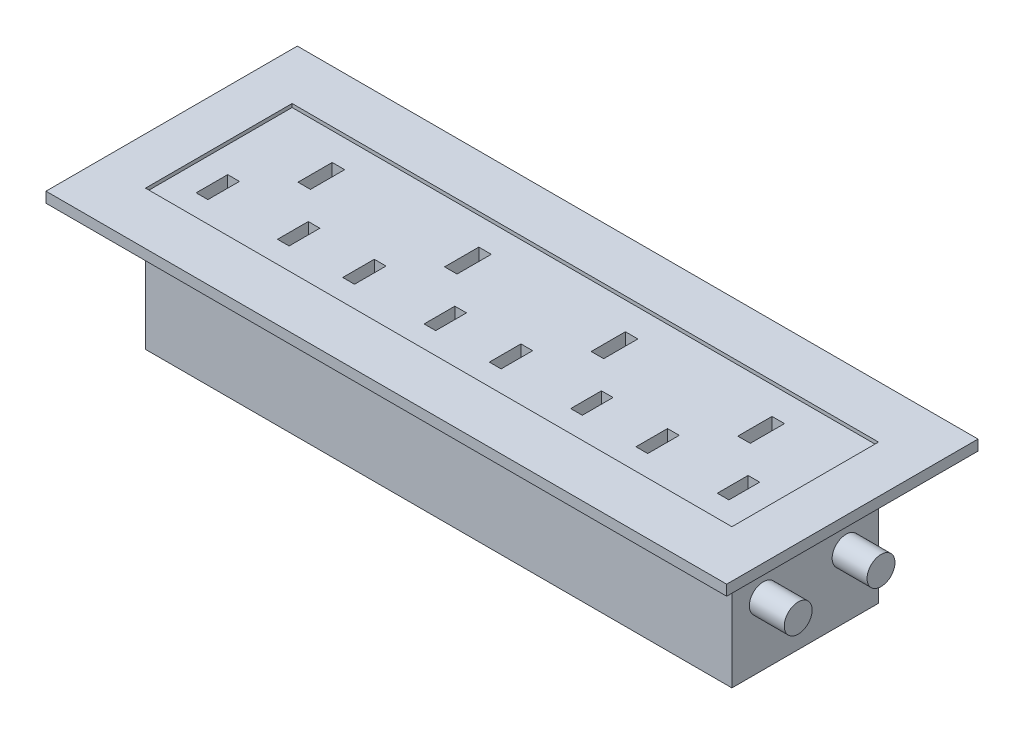
SolidWorks part; units mm, degrees
ref_plane "前视基准面" through (0, 0, 0) normal (0, 0, 1) x (1, 0, 0)
ref_plane "上视基准面" through (0, 0, 0) normal (0, 1, 0) x (1, 0, 0)
ref_plane "右视基准面" through (0, 0, 0) normal (1, 0, 0) x (0, 0, -1)
sketch "草图1" plane through (0, 0, 0) normal (0, 1, 0) x (1, 0, 0)
  line L1 (-97.5, 36) -> (97.5, 36)
  line L2 (-97.5, 36) -> (-97.5, -36)
  line L3 (-97.5, -36) -> (97.5, -36)
  line L4 (97.5, 36) -> (97.5, -36)
  line L5 (-97.5, 36) -> (97.5, -36) construction
  line L6 (-97.5, -36) -> (97.5, 36) construction
  point P0 (0, 0)
  dimension "D1" = 195
  dimension "D2" = 72
extrude "凸台-拉伸1" add sketch "草图1" along normal blind 3
sketch "草图2" plane through (0, 3, 0) normal (0, 1, 0) x (1, 0, 0)
  line L1 (-84, 21) -> (84, 21)
  line L2 (-84, 21) -> (-84, -21)
  line L3 (-84, -21) -> (84, -21)
  line L4 (84, 21) -> (84, -21)
  line L5 (-84, 21) -> (84, -21) construction
  line L6 (-84, -21) -> (84, 21) construction
  point P0 (0, 0)
  dimension "D1" = 168
  dimension "D2" = 42
extrude "凸台-拉伸2" add sketch "草图2" against normal blind 40
extrude "切除-拉伸1" cut sketch "草图2<2>" against normal blind 1
sketch "草图2<2>" plane through (0, 3, 0) normal (0, 1, 0) x (1, 0, 0) same geometry as "草图2"
sketch "草图3" plane through (84, 0, 0) normal (1, 0, 0) x (0, 0, -1)
  circle A0 centre (-12.0094, -19.1516) radius 4
  dimension "D1" = 8
extrude "凸台-拉伸3" add sketch "草图3" along normal blind 10
sketch "草图4" plane through (84, 0, 0) normal (1, 0, 0) x (0, 0, -1)
  circle A0 centre (11.7157, -19.2283) radius 4
  dimension "D1" = 8
extrude "凸台-拉伸4" add sketch "草图4" along normal blind 10
sketch "草图5" plane through (0, 2, 0) normal (0, 1, 0) x (1, 0, 0)
  line L0 (0, 21) -> (0, -21) construction
  line L1 (84, 21) -> (-84, 21) construction
  line L2 (-84, -21) -> (84, -21) construction
  line L3 (-42, 21) -> (-42, -21) construction
  line L4 (-84, -21) -> (84, -21) construction
  line L5 (42, 21) -> (42, -21) construction
  line L6 (84, 21) -> (-84, 21) construction
  dimension "D1" = 42
  dimension "D2" = 42
sketch "草图6" plane through (0, 2, 0) normal (0, 1, 0) x (1, 0, 0)
  line L0 (-22.6315, 13.1172) -> (-22.6315, 3.3157)
  line L1 (-64.6315, 13.1172) -> (-61.0518, 13.1172)
  line L2 (-64.6315, 13.1172) -> (-64.6315, 3.3157)
  line L3 (-64.6315, 3.3157) -> (-61.0518, 3.3157)
  line L4 (-61.0518, 13.1172) -> (-61.0518, 3.3157)
  line L5 (-22.6315, 13.1172) -> (-19.0518, 13.1172)
  line L6 (-19.0518, 13.1172) -> (-19.0518, 3.3157)
  line L7 (-22.6315, 3.3157) -> (-19.0518, 3.3157)
  line L8 (19.3685, 13.1172) -> (19.3685, 3.3157)
  line L9 (19.3685, 13.1172) -> (22.9482, 13.1172)
  line L10 (22.9482, 13.1172) -> (22.9482, 3.3157)
  line L11 (19.3685, 3.3157) -> (22.9482, 3.3157)
  line L12 (61.3685, 13.1172) -> (61.3685, 3.3157)
  line L13 (61.3685, 13.1172) -> (64.9482, 13.1172)
  line L14 (64.9482, 13.1172) -> (64.9482, 3.3157)
  line L15 (61.3685, 3.3157) -> (64.9482, 3.3157)
  dimension "D1" = 4
sketch "草图7" plane through (0, 2, 0) normal (0, 1, 0) x (1, 0, 0)
  line L0 (-34.5817, -4.8673) -> (-34.5817, -13.9105)
  line L1 (-76.5817, -4.8673) -> (-73.211, -4.8673)
  line L2 (-76.5817, -4.8673) -> (-76.5817, -13.9105)
  line L3 (-76.5817, -13.9105) -> (-73.211, -13.9105)
  line L4 (-73.211, -4.8673) -> (-73.211, -13.9105)
  line L5 (-34.5817, -4.8673) -> (-31.211, -4.8673)
  line L6 (-31.211, -4.8673) -> (-31.211, -13.9105)
  line L7 (-34.5817, -13.9105) -> (-31.211, -13.9105)
  line L8 (7.4183, -4.8673) -> (7.4183, -13.9105)
  line L9 (7.4183, -4.8673) -> (10.789, -4.8673)
  line L10 (10.789, -4.8673) -> (10.789, -13.9105)
  line L11 (7.4183, -13.9105) -> (10.789, -13.9105)
  line L12 (49.4183, -4.8673) -> (49.4183, -13.9105)
  line L13 (49.4183, -4.8673) -> (52.789, -4.8673)
  line L14 (52.789, -4.8673) -> (52.789, -13.9105)
  line L15 (49.4183, -13.9105) -> (52.789, -13.9105)
  dimension "D1" = 4
extrude "切除-拉伸2" cut sketch "草图7" against normal blind 25
extrude "切除-拉伸3" cut sketch "草图6" against normal blind 25
sketch "草图8" plane through (0, 2, 0) normal (0, 1, 0) x (1, 0, 0)
  line L0 (-11.4032, -4.9654) -> (-11.4032, -13.7851)
  line L1 (-53.4032, -4.9654) -> (-50.0749, -4.9654)
  line L2 (-53.4032, -4.9654) -> (-53.4032, -13.7851)
  line L3 (-53.4032, -13.7851) -> (-50.0749, -13.7851)
  line L4 (-50.0749, -4.9654) -> (-50.0749, -13.7851)
  line L5 (-11.4032, -4.9654) -> (-8.0749, -4.9654)
  line L6 (-8.0749, -4.9654) -> (-8.0749, -13.7851)
  line L7 (-11.4032, -13.7851) -> (-8.0749, -13.7851)
  line L8 (30.5968, -4.9654) -> (30.5968, -13.7851)
  line L9 (30.5968, -4.9654) -> (33.9251, -4.9654)
  line L10 (33.9251, -4.9654) -> (33.9251, -13.7851)
  line L11 (30.5968, -13.7851) -> (33.9251, -13.7851)
  line L12 (72.5968, -4.9654) -> (72.5968, -13.7851)
  line L13 (72.5968, -4.9654) -> (75.9251, -4.9654)
  line L14 (75.9251, -4.9654) -> (75.9251, -13.7851)
  line L15 (72.5968, -13.7851) -> (75.9251, -13.7851)
  dimension "D1" = 4
extrude "切除-拉伸4" cut sketch "草图8" against normal blind 25
